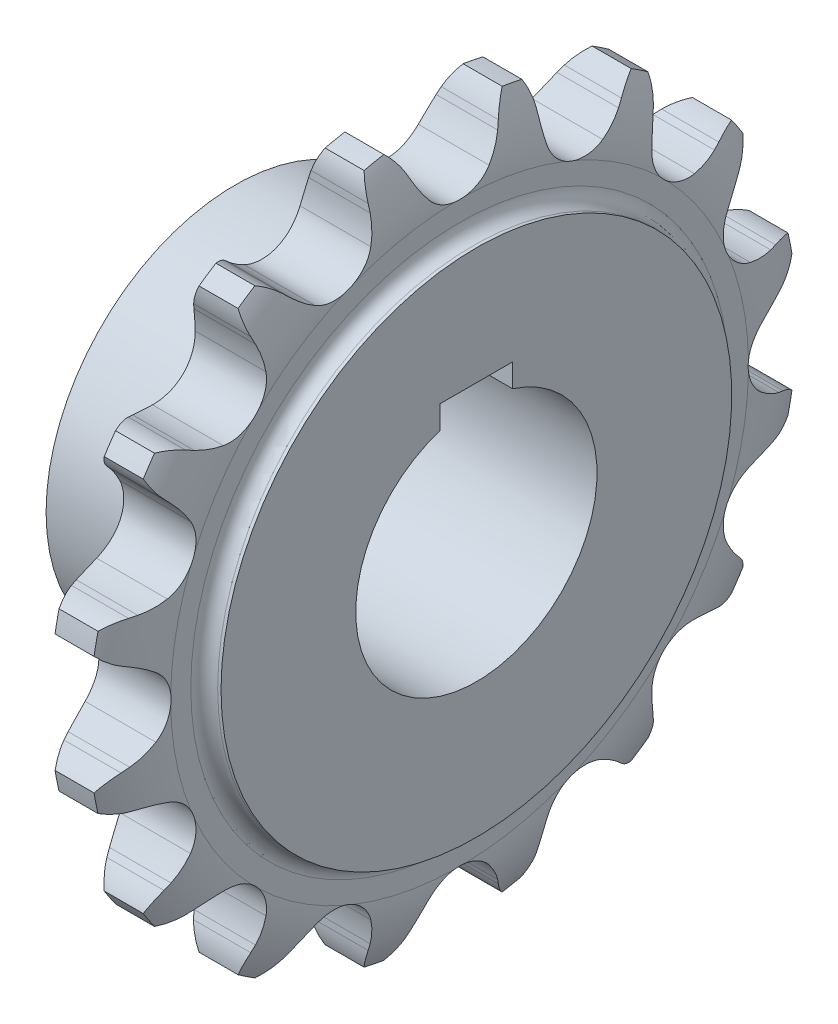
SolidWorks part; units mm, degrees
material "AISI 1020"
ref_plane "Front" through (0, 0, 0) normal (0, 0, 1) x (1, 0, 0)
ref_plane "Top" through (0, 0, 0) normal (0, 1, 0) x (1, 0, 0)
ref_plane "Right" through (0, 0, 0) normal (1, 0, 0) x (0, 0, -1)
sketch "Sketch1" plane through (0, 0, 0) normal (0, 0, 1) x (1, 0, 0)
  line L0 (-4, 0) -> (4, 0) construction
  line L1 (-13.1513, 0) -> (-13.1513, 63.5)
  line L2 (-13.1513, 63.5) -> (-12.3165, 63.5)
  line L3 (-8.9775, 66.839) -> (-8.9775, 71.8476)
  line L4 (-4.85, 88) -> (4.85, 88)
  line L5 (8.9775, 71.8476) -> (8.9775, 66.839)
  line L6 (12.3165, 63.5) -> (13.1513, 63.5)
  line L7 (13.1513, 63.5) -> (13.1513, 0)
  line L8 (13.1513, 0) -> (-13.1513, 0)
  line L9 (0, 0) -> (0, 88) construction
  line L10 (-7.669, 81.3726) -> (7.669, 81.3726) construction
  line L11 (-7.669, -81.3726) -> (7.669, -81.3726) construction
  line L13 (-8.9775, 71.8476) -> (3.7984, 71.8476) construction
  line L14 (-8.9775, -71.8476) -> (3.7984, -71.8476) construction
  arc A0 (-4.85, 88) -> (-8.9775, 71.8476) centre (22.7687, 72.3389) ccw
  arc A1 (4.85, 88) -> (8.9775, 71.8476) centre (-22.7687, 72.3389) cw
  arc A2 (8.9775, 66.839) -> (12.3165, 63.5) centre (12.3165, 66.839) ccw
  arc A3 (-12.3165, 63.5) -> (-8.9775, 66.839) centre (-12.3165, 66.839) ccw
  point P30 (8.9775, 63.5)
  point P33 (-8.9775, 63.5)
  point P34 (24, 26.331)
  point P36 (43.05, 26.331)
  point P37 (24, 21.8279)
  point P38 (54.18, 21.8279)
  point P39 (24, 17.1531)
  point P40 (42.9, 17.1531)
  point P41 (24, 13.3224)
  point P42 (59.76, 13.3224)
  point P43 (24, 30.8002)
  point P44 (40, 30.8002)
  point P45 (24, 35.1098)
  point P46 (55.75, 35.1098)
  dimension "D1" = 8.3476
  dimension "rx" = 31.75
  dimension "D3" = 3.339
  dimension "d" = 162.7451
  dimension "p" = 31.75
  dimension "z" = 16
  dimension "da" = 176
  dimension "df" = 143.6951
  dimension "dr" = 19.05
  dimension "dg" = 127
  dimension "h" = 30.18
  dimension "bf1" = 17.955
  dimension "b1" = 18.9
  dimension "ba" = 4.1275
  dimension "D2" = 4.1738
  dimension "pt" = 35.76
revolve "Revolve" add sketch "Sketch1" angle 360 about L0
ref_axis "Axis1" through (-8.5448, 0, 0) along (1, 0, 0)
sketch "Sketch2" plane through (0, 0, 0) normal (1, 0, 0) x (0, 0, -1)
  line L0 (0, 0) -> (0, 88) construction
  line L1 (0, 0) -> (-17.1679, 86.3091) construction
  line L2 (0, 0) -> (-33.6761, 81.3014) construction
  line L3 (7.5045, 75.3495) -> (24.1335, 62.0034) construction
  line L4 (10.7834, 80.7001) -> (-11.8854, 90.9116) construction
  line L5 (0, 0) -> (17.1679, 86.3091) construction
  line L6 (10.7834, 80.7001) -> (11.5042, 82.3003)
  line L7 (-10.7834, 80.7001) -> (-11.5042, 82.3003)
  circle A0 centre (0, 0) radius 88 construction
  arc A1 (7.5045, 75.3495) -> (-7.5045, 75.3495) centre (0, 81.3726) cw
  arc A2 (7.5045, 75.3495) -> (10.7834, 80.7001) centre (-11.8854, 90.9116) ccw
  arc A3 (14.6923, 86.7648) -> (11.5042, 82.3003) centre (24.2891, 76.5412) ccw
  arc A4 (-7.5045, 75.3495) -> (-10.7834, 80.7001) centre (11.8854, 90.9116) cw
  arc A5 (-14.6923, 86.7648) -> (-11.5042, 82.3003) centre (-24.2891, 76.5412) cw
  arc A7 (14.6923, 86.7648) -> (-14.6923, 86.7648) centre (0, 0) ccw
  dimension "r1" = 9.6226
  dimension "r3" = 14.0222
  dimension "D1" = 22.5
  dimension "D2" = 11.25
  dimension "av2" = 51.25
  dimension "M" = 11.8854
  dimension "T" = 9.5391
  dimension "beta" = 14.5
  dimension "yv2" = 13
  dimension "bc" = 1.7551
extrude "ExtrudeCutOne" cut sketch "Sketch2" against normal mid plane 26.3026
pattern_circular "PatternOne" count 16 over 360 about axis through (-4, 0, 0) along (1, 0, 0) of "ExtrudeCutOne"
sketch "Cut-ExtrudeA" plane through (0, 0, 0) normal (1, 0, 0) x (0, 0, -1)
  circle A0 centre (0, 0) radius 30
sketch "SketchKey" plane through (0, 0, 0) normal (1, 0, 0) x (0, 0, -1)
  line L1 (-9, 15) -> (9, 15)
  line L2 (-9, 15) -> (-9, 34.4)
  line L3 (-9, 34.4) -> (9, 34.4)
  line L4 (9, 15) -> (9, 34.4)
extrude "Cut-ExtrudeB" cut sketch "SketchKey" against normal through all and the other way through all
sketch "草图3" plane through (13.1513, 0, 0) normal (1, 0, 0) x (0, 0, -1)
  circle A0 centre (0, 0) radius 30
  dimension "D1" = 60
extrude "切除-拉伸3" cut sketch "草图3" against normal up to next
sketch "草图4" plane through (-13.1513, 0, 0) normal (-1, 0, 0) x (0, 0, 1)
  line L0 (9, 34.4) -> (9, 28.6182) construction
  line L1 (9, 34.4) -> (9, 28.6182)
  line L3 (-9, 34.4) -> (9, 34.4) construction
  line L4 (-9, 34.4) -> (9, 34.4)
  line L5 (-9, 28.6182) -> (-9, 34.4) construction
  line L6 (-9, 28.6182) -> (-9, 34.4)
  arc A0 (-9, 28.6182) -> (9, 28.6182) centre (0, 0) ccw construction
  arc A1 (-9, 28.6182) -> (9, 28.6182) centre (0, 0) ccw
  circle A5 centre (0, 0) radius 47
  dimension "D1" = 94
extrude "凸台-拉伸1" add sketch "草图4" along normal blind 33.7
fillet "圆角1" radius 5 1 edges at (-13.1513, 0, -47)
